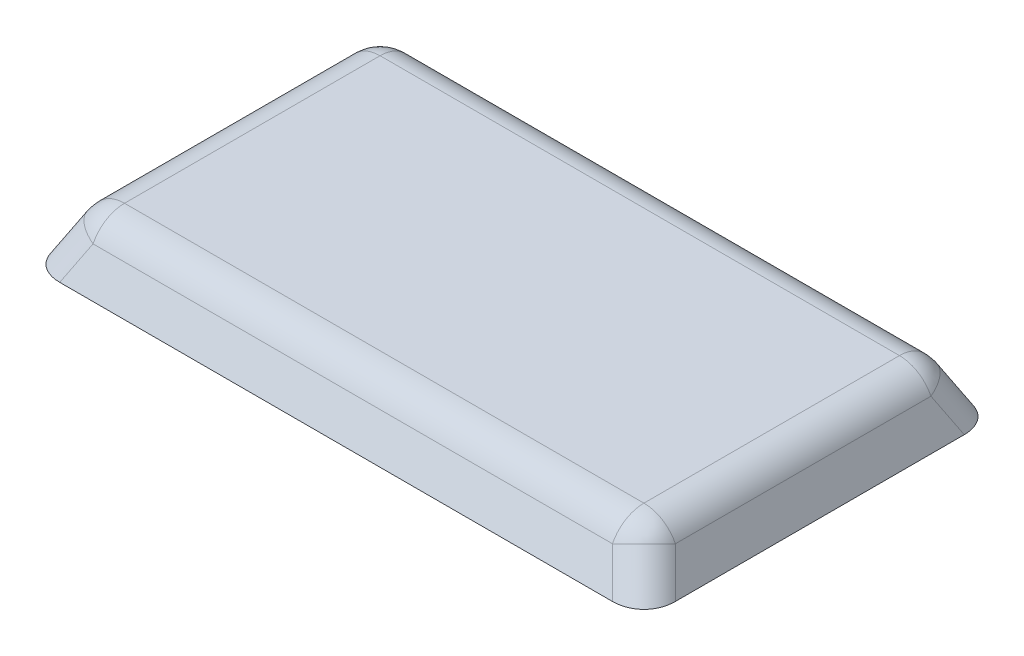
SolidWorks part; units mm, degrees
ref_plane "Front Plane" through (0, 0, 0) normal (0, 0, 1) x (1, 0, 0)
ref_plane "Top Plane" through (0, 0, 0) normal (0, 1, 0) x (1, 0, 0)
ref_plane "Right Plane" through (0, 0, 0) normal (1, 0, 0) x (0, 0, -1)
sketch "Sketch1" plane through (0, 0, 0) normal (0, 1, 0) x (1, 0, 0)
  line L1 (-35, -20) -> (35, -20)
  line L2 (-35, -20) -> (-35, 20)
  line L3 (-35, 20) -> (35, 20)
  line L4 (35, -20) -> (35, 20)
  line L5 (-35, -20) -> (35, 20) construction
  line L6 (-35, 20) -> (35, -20) construction
  point P0 (0, 0)
  dimension "D1" = 40
  dimension "D2" = 70
ref_plane "Plane1" through (0, 6, 0) normal (0, 1, 0) x (1, 0, 0)
sketch "Sketch2" plane through (0, 6, 0) normal (0, 1, 0) x (1, 0, 0)
  line L0 (-35, 20) -> (35, 20) construction
  line L1 (-32, -17) -> (32, -17)
  line L2 (-32, -17) -> (-32, 17)
  line L3 (-32, 17) -> (32, 17)
  line L4 (32, -17) -> (32, 17)
  line L5 (-32, -17) -> (32, 17) construction
  line L6 (-32, 17) -> (32, -17) construction
  line L7 (35, -20) -> (35, 20) construction
  point P0 (0, 0)
  dimension "D1" = 3
  dimension "D2" = 3
loft "Loft1" add profiles "Sketch1", "Sketch2" connector at (-35, 0, 20) connector at (-32, 6, 17)
fillet "Fillet1" radius 4 8 edges
